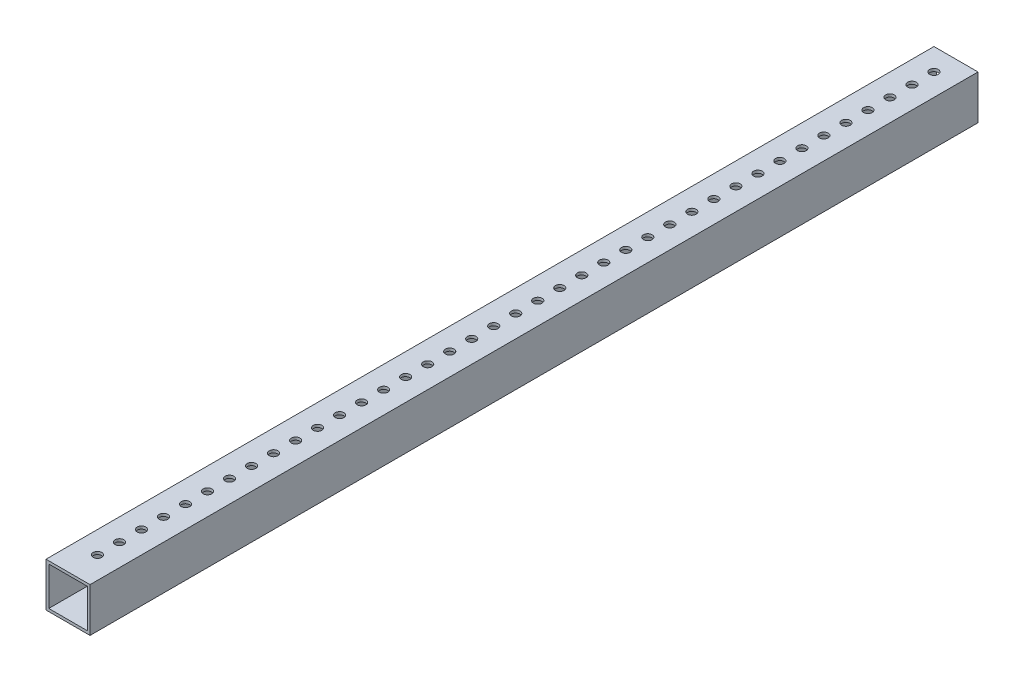
SolidWorks part; units mm, degrees
material "6061-T6 (SS)"
ref_plane "Front Plane" through (0, 0, 0) normal (0, 0, 1) x (1, 0, 0)
ref_plane "Top Plane" through (0, 0, 0) normal (0, 1, 0) x (1, 0, 0)
ref_plane "Right Plane" through (0, 0, 0) normal (1, 0, 0) x (0, 0, -1)
sketch "Sketch1" plane through (0, 0, 0) normal (0, 0, 1) x (1, 0, 0)
  line L1 (-12.7, -12.7) -> (12.7, -12.7)
  line L2 (-12.7, -12.7) -> (-12.7, 12.7)
  line L3 (-12.7, 12.7) -> (12.7, 12.7)
  line L4 (12.7, -12.7) -> (12.7, 12.7)
  line L5 (-12.7, -12.7) -> (12.7, 12.7) construction
  line L6 (-12.7, 12.7) -> (12.7, -12.7) construction
  point P0 (0, 0)
  dimension "D1" = 25.4
  dimension "D2" = 25.4
extrude "Boss-Extrude1" add sketch "Sketch1" along normal mid plane 512.2926
shell "Shell1" thickness 1.5875 removed face at (0, 0, -256.1463) removed face at (0, 0, 256.1463)
sketch "Sketch3" plane through (0, 0, 0) normal (0, 1, 0) x (1, 0, 0)
  line L0 (12.7, 256.1463) -> (-12.7, 256.1463) construction
  circle A0 centre (0, 243.4463) radius 2.4892
  circle A1 centre (0, 230.7463) radius 2.4892
  circle A2 centre (0, 218.0463) radius 2.4892
  circle A3 centre (0, 205.3463) radius 2.4892
  circle A4 centre (0, 192.6463) radius 2.4892
  circle A5 centre (0, 179.9463) radius 2.4892
  circle A6 centre (0, 167.2463) radius 2.4892
  circle A7 centre (0, 154.5463) radius 2.4892
  circle A8 centre (0, 141.8463) radius 2.4892
  circle A9 centre (0, 129.1463) radius 2.4892
  circle A10 centre (0, 116.4463) radius 2.4892
  circle A11 centre (0, 103.7463) radius 2.4892
  circle A12 centre (0, 91.0463) radius 2.4892
  circle A13 centre (0, 78.3463) radius 2.4892
  circle A14 centre (0, 65.6463) radius 2.4892
  circle A15 centre (0, 52.9463) radius 2.4892
  circle A16 centre (0, 40.2463) radius 2.4892
  circle A17 centre (0, 27.5463) radius 2.4892
  circle A18 centre (0, 14.8463) radius 2.4892
  circle A19 centre (0, 2.1463) radius 2.4892
  circle A20 centre (0, -10.5537) radius 2.4892
  circle A21 centre (0, -23.2537) radius 2.4892
  circle A22 centre (0, -35.9537) radius 2.4892
  circle A23 centre (0, -48.6537) radius 2.4892
  circle A24 centre (0, -61.3537) radius 2.4892
  circle A25 centre (0, -74.0537) radius 2.4892
  circle A26 centre (0, -86.7537) radius 2.4892
  circle A27 centre (0, -99.4537) radius 2.4892
  circle A28 centre (0, -112.1537) radius 2.4892
  circle A29 centre (0, -124.8537) radius 2.4892
  circle A30 centre (0, -137.5537) radius 2.4892
  circle A31 centre (0, -150.2537) radius 2.4892
  circle A32 centre (0, -162.9537) radius 2.4892
  circle A33 centre (0, -175.6537) radius 2.4892
  circle A34 centre (0, -188.3537) radius 2.4892
  circle A35 centre (0, -201.0537) radius 2.4892
  circle A36 centre (0, -213.7537) radius 2.4892
  circle A37 centre (0, -226.4537) radius 2.4892
  circle A38 centre (0, -239.1537) radius 2.4892
  point P4 (0, 256.1463)
  dimension "D1" = 4.9784
  dimension "D2" = 12.7
  dimension "D4" = 12.7
  dimension "D3" = 39
extrude "Cut-Extrude1" cut sketch "Sketch3" against normal through all both and the other way through all
